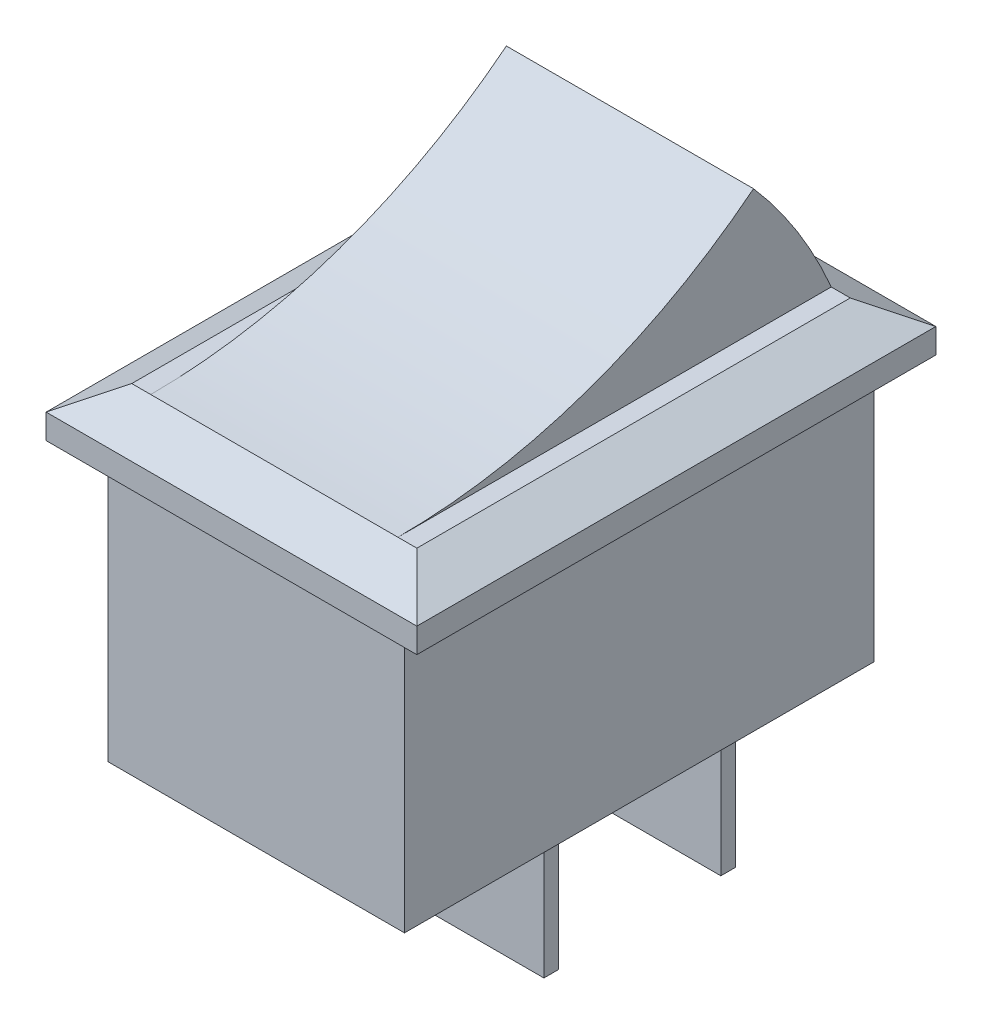
SolidWorks part; units mm, degrees
ref_plane "Front Plane" through (0, 0, 0) normal (0, 0, 1) x (1, 0, 0)
ref_plane "Top Plane" through (0, 0, 0) normal (0, 1, 0) x (1, 0, 0)
ref_plane "Right Plane" through (0, 0, 0) normal (1, 0, 0) x (0, 0, -1)
sketch "Sketch1" plane through (0, 0, 0) normal (0, 1, 0) x (1, 0, 0)
  line L1 (-6, -9.5) -> (6, -9.5)
  line L2 (-6, -9.5) -> (-6, 9.5)
  line L3 (-6, 9.5) -> (6, 9.5)
  line L4 (6, -9.5) -> (6, 9.5)
  line L5 (-6, -9.5) -> (6, 9.5) construction
  line L6 (-6, 9.5) -> (6, -9.5) construction
  point P0 (0, 0)
  dimension "D1" = 12
  dimension "D2" = 19
extrude "Boss-Extrude1" add sketch "Sketch1" along normal blind 11
sketch "Sketch2" plane through (0, 11, 0) normal (0, 1, 0) x (1, 0, 0)
  line L1 (7.5, -10.5) -> (-7.5, -10.5)
  line L2 (7.5, -10.5) -> (7.5, 10.5)
  line L3 (7.5, 10.5) -> (-7.5, 10.5)
  line L4 (-7.5, -10.5) -> (-7.5, 10.5)
  line L5 (7.5, -10.5) -> (-7.5, 10.5) construction
  line L6 (7.5, 10.5) -> (-7.5, -10.5) construction
  line L7 (5, -8) -> (-5, -8)
  line L8 (5, -8) -> (5, 8)
  line L9 (5, 8) -> (-5, 8)
  line L10 (-5, -8) -> (-5, 8)
  line L11 (5, -8) -> (-5, 8) construction
  line L12 (5, 8) -> (-5, -8) construction
  point P0 (0, 0)
  point P6 (0, 0)
  dimension "D1" = 15
  dimension "D2" = 21
  dimension "D3" = 10
  dimension "D4" = 16
extrude "Boss-Extrude2" add sketch "Sketch2" along normal blind 2
chamfer "Chamfer1" distance 1 angle 60 4 edges at (0, 13, -10.5) (-7.5, 13, 0) (0, 13, 10.5) (7.5, 13, 0) first distance on face at (0, 12, -10.5) first distance on face at (-7.5, 12, 0) first distance on face at (0, 12, 10.5) first distance on face at (7.5, 12, 0)
sketch "Sketch3" plane through (-5, 0, 0) normal (1, 0, 0) x (0, 0, -1)
  line L1 (-8.7679, 13) -> (-8.7679, 24.5724) construction
  line L2 (-8.7679, 13) -> (-8.7679, 0) construction
  line L3 (-9.5, 0) -> (9.5, 0) construction
  line L4 (-8.7679, 24.5724) -> (-8.7679, 36.1449) construction
  line L5 (-9.5, 5.5) -> (-8.7679, 5.5) construction
  line L6 (-9.5, 11) -> (-9.5, 0) construction
  line L7 (-8.7679, 13) -> (-10.5, 12) construction
  line L10 (-8.7679, 13) -> (-8.7679, 12)
  line L11 (-8.7679, 12) -> (9.1627, 12)
  line L12 (10.5, 12) -> (-10.5, 12) construction
  circle A1 centre (-8.7679, 5.5) radius 19.0724 construction
  circle A3 centre (-8.7679, 36.1449) radius 23.1449 construction
  arc A4 (5.6222, 18.0173) -> (-8.7679, 13) centre (-8.7679, 36.1449) cw
  arc A5 (5.6222, 18.0173) -> (9.1627, 12) centre (-8.7679, 5.5) cw
extrude "Boss-Extrude3" add sketch "Sketch3" along normal up to surface (10 mm away) up to face at (5, 12, 0)
sketch "Sketch4" plane through (0, 0, 0) normal (0, -1, 0) x (1, 0, 0)
  line L0 (0, -7.2) -> (0, -0.04) construction
  line L1 (2.4, -7.5) -> (-2.4, -7.5)
  line L2 (2.4, -7.5) -> (2.4, -6.9)
  line L3 (2.4, -6.9) -> (-2.4, -6.9)
  line L4 (-2.4, -7.5) -> (-2.4, -6.9)
  line L5 (2.4, -7.5) -> (-2.4, -6.9) construction
  line L6 (2.4, -6.9) -> (-2.4, -7.5) construction
  line L7 (2.4, -0.34) -> (-2.4, -0.34)
  line L8 (2.4, -0.34) -> (2.4, 0.26)
  line L9 (2.4, 0.26) -> (-2.4, 0.26)
  line L10 (-2.4, -0.34) -> (-2.4, 0.26)
  line L11 (2.4, -0.34) -> (-2.4, 0.26) construction
  line L12 (2.4, 0.26) -> (-2.4, -0.34) construction
  line L13 (0, 0) -> (0, -0.04) construction
  line L15 (6, -9.5) -> (-6, -9.5) construction
  point P0 (0, -7.2)
  point P5 (0, -0.04)
  dimension "D1" = 0.6
  dimension "D2" = 4.8
  dimension "D3" = 2
  dimension "D4" = 6.56
extrude "Boss-Extrude4" add sketch "Sketch4" along normal blind 8
sketch "Sketch6" plane through (0, -8, 0) normal (0, -1, 0) x (1, 0, 0)
  line L0 (-2.4, -0.04) -> (2.4, -0.04) construction
  line L1 (-2.4, 0.26) -> (-2.4, -0.34) construction
  line L2 (2.4, -0.34) -> (2.4, 0.26) construction
  line L3 (0, 0.26) -> (0, -0.34) construction
  line L4 (2.4, 0.26) -> (-2.4, 0.26) construction
  line L5 (-2.4, -0.34) -> (2.4, -0.34) construction
  line L6 (0, -6.9) -> (0, -7.5) construction
  line L7 (2.4, -6.9) -> (-2.4, -6.9) construction
  line L8 (-2.4, -7.5) -> (2.4, -7.5) construction
  line L9 (2.4, -7.2) -> (-2.4, -7.2) construction
  line L10 (2.4, -7.5) -> (2.4, -6.9) construction
  line L11 (-2.4, -6.9) -> (-2.4, -7.5) construction
  point P12 (0, -0.04)
  point P25 (0, -7.2)
other "CPoint3" parameters "Diameter"=3, "StubLength"=4.5
ref_axis "Axis3" through (0, -18, -0.04) along (0, 1, 0)
other "CPoint4" parameters "Diameter"=3, "StubLength"=4.5
ref_axis "Axis4" through (0, -18, -7.2) along (0, 1, 0)
